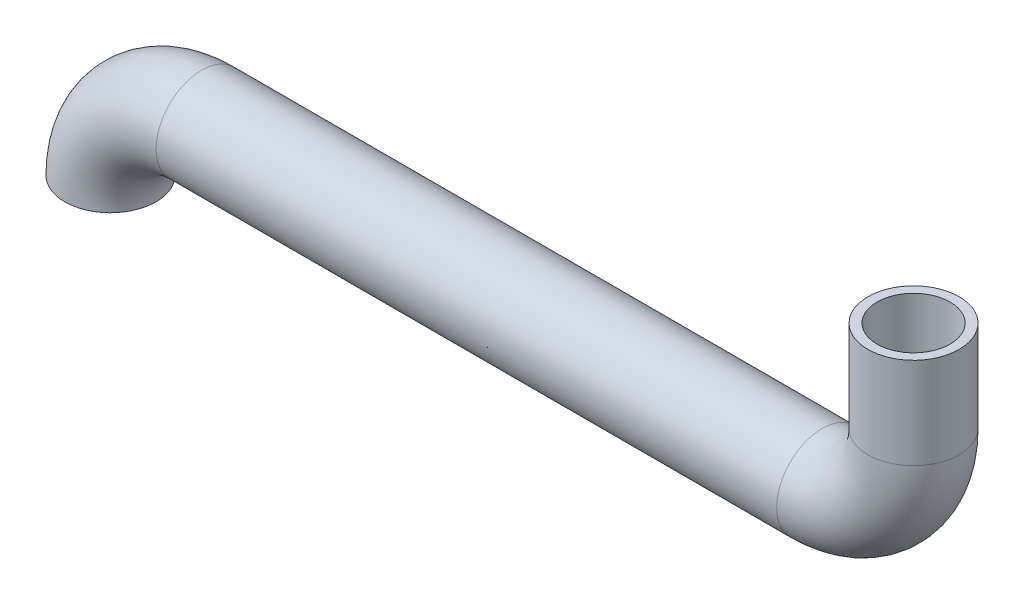
SolidWorks part; units mm, degrees
ref_plane "前视基准面" through (0, 0, 0) normal (0, 0, 1) x (1, 0, 0)
ref_plane "上视基准面" through (0, 0, 0) normal (0, 1, 0) x (1, 0, 0)
ref_plane "右视基准面" through (0, 0, 0) normal (1, 0, 0) x (0, 0, -1)
other "Configuration Table"
sketch "草图1" plane through (0, 0, 0) normal (0, 0, 1) x (1, 0, 0)
  line L0 (0, 10) -> (68, 10)
  line L1 (78, 20) -> (78, 30)
  line L2 (-1000, 0) -> (49000, 0) construction
  arc A0 (0, 10) -> (-10, 0) centre (0, 0) ccw
  arc A1 (68, 10) -> (78, 20) centre (68, 20) ccw
  point P8 (78, 10)
  dimension "D1" = 20
  dimension "D4" = 10
  dimension "D2" = 78
  dimension "D3" = 20
sweep "扫描-薄件1" add path "草图1" circular profile diameter 10 parameters "D1"=1, "D3"=10
